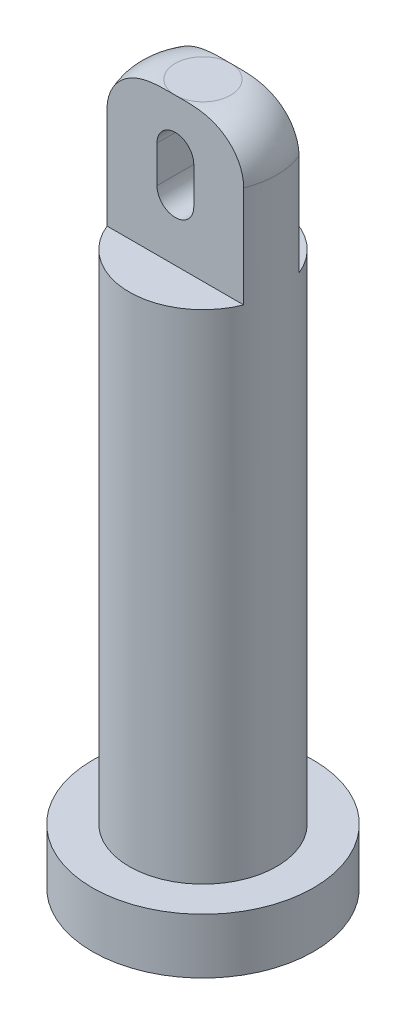
SolidWorks part; units mm, degrees
ref_plane "Front Plane" through (0, 0, 0) normal (0, 0, 1) x (1, 0, 0)
ref_plane "Top Plane" through (0, 0, 0) normal (0, 1, 0) x (1, 0, 0)
ref_plane "Right Plane" through (0, 0, 0) normal (1, 0, 0) x (0, 0, -1)
sketch "Sketch1" plane through (0, 0, 0) normal (0, 1, 0) x (1, 0, 0)
  circle A0 centre (0, 0) radius 3
  dimension "D1" = 6
extrude "Boss-Extrude1" add sketch "Sketch1" along normal blind 1.5
sketch "Sketch2" plane through (0, 1.5, 0) normal (0, 1, 0) x (1, 0, 0)
  circle A0 centre (0, 0) radius 2
  dimension "D1" = 4
extrude "Boss-Extrude2" add sketch "Sketch2" along normal blind 13.5
sketch "Sketch6" plane through (0, 15, 0) normal (0, 1, 0) x (1, 0, 0)
  line L1 (1.854, 0.75) -> (-1.854, 0.75)
  line L3 (1.854, -0.75) -> (-1.854, -0.75)
  line L5 (0, -0.75) -> (0, 0.75) construction
  line L6 (1.854, 0) -> (-1.854, 0) construction
  arc A0 (1.854, -0.75) -> (1.854, 0.75) centre (0, 0) ccw
  circle A1 centre (0, 0) radius 2
  arc A2 (-1.854, 0.75) -> (-1.854, -0.75) centre (0, 0) ccw
  dimension "D2" = 1.5
  dimension "D1" = 0
extrude "Boss-Extrude3" add sketch "Sketch6" along normal blind 4
sketch "Sketch7" plane through (0, 0, 0.75) normal (0, 0, 1) x (1, 0, 0)
  line L0 (0, 19) -> (0, 17) construction
  line L1 (0, 16.6267) -> (0, 17.6267) construction
  line L2 (-0.5, 16.6267) -> (-0.5, 17.6267)
  line L3 (0.5, 16.6267) -> (0.5, 17.6267)
  line L4 (-1.854, 15) -> (1.854, 15)
  line L5 (1.854, 15) -> (1.854, 19)
  line L6 (1.854, 19) -> (-1.854, 19)
  line L7 (-1.854, 19) -> (-1.854, 15)
  line L8 (-1.854, 15) -> (1.854, 15)
  line L9 (1.854, 15) -> (1.854, 19)
  line L10 (1.854, 19) -> (-1.854, 19)
  line L11 (-1.854, 19) -> (-1.854, 15)
  arc A1 (-0.5, 16.6267) -> (0.5, 16.6267) centre (0, 16.6267) ccw
  arc A2 (0.5, 17.6267) -> (-0.5, 17.6267) centre (0, 17.6267) ccw
  point P9 (0, 17.1267)
  dimension "D3" = 1
  dimension "D2" = 2
  dimension "D4" = 1
  dimension "D1" = 0
extrude "Cut-Extrude1" cut sketch "Sketch7" against normal blind 3 contours L3 A2 L2 A1
fillet "Fillet5" radius 1.25 2 edges at (2, 19, 0) (-2, 19, 0)
